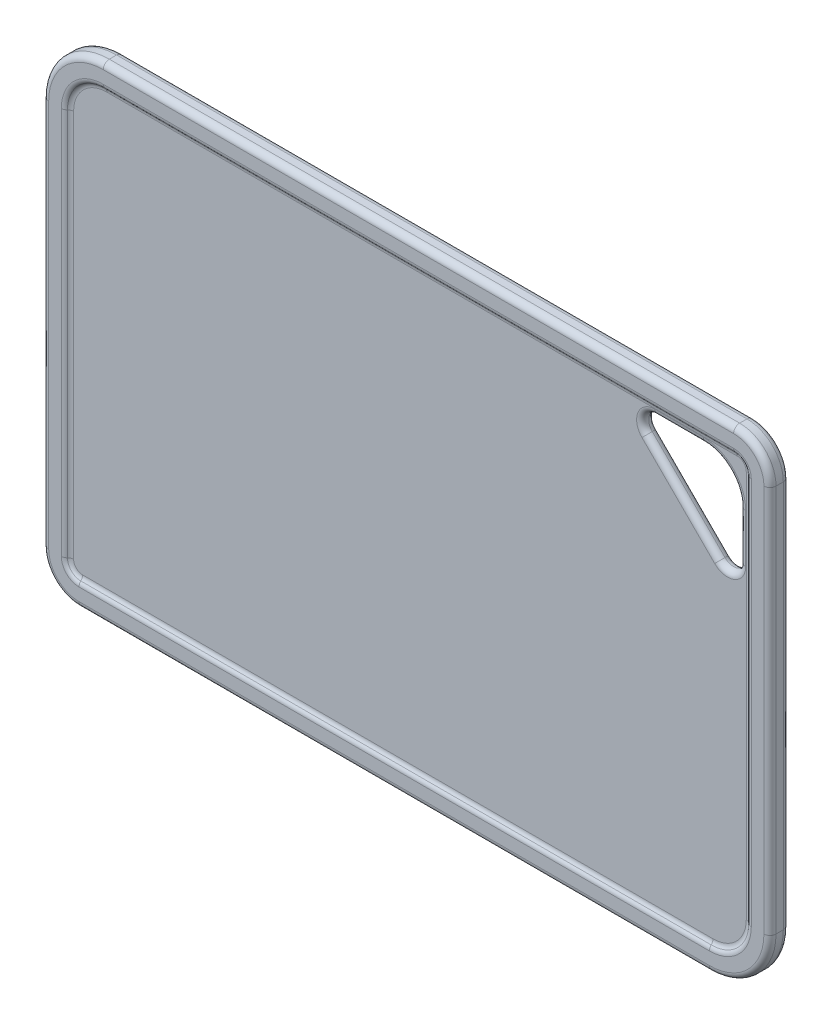
SolidWorks part; units mm, degrees
ref_plane "Front Plane" through (0, 0, 0) normal (0, 0, 1) x (1, 0, 0)
ref_plane "Top Plane" through (0, 0, 0) normal (0, 1, 0) x (1, 0, 0)
ref_plane "Right Plane" through (0, 0, 0) normal (1, 0, 0) x (0, 0, -1)
sketch "Sketch1" plane through (0, 0, 0) normal (0, 0, 1) x (1, 0, 0)
  line L1 (-190.5, -127) -> (190.5, -127)
  line L2 (-190.5, -127) -> (-190.5, 127)
  line L3 (-190.5, 127) -> (190.5, 127)
  line L4 (190.5, -127) -> (190.5, 127)
  line L5 (-190.5, -127) -> (190.5, 127) construction
  line L6 (-190.5, 127) -> (190.5, -127) construction
  point P0 (0, 0)
  dimension "D1" = 381
  dimension "D2" = 254
extrude "Boss-Extrude1" add sketch "Sketch1" along normal mid plane 6.35
fillet "Fillet5" radius 19.05 2 edges at (-190.5, -127, 0) (190.5, 127, 0)
fillet "Fillet4" radius 31.75 2 edges at (190.5, -127, 0) (-190.5, 127, 0)
sketch "Sketch2" plane through (0, 0, 3.175) normal (0, 0, 1) x (1, 0, 0)
  line L4 (-171.45, -127) -> (158.75, -127)
  line L5 (190.5, -95.25) -> (190.5, 107.95)
  line L6 (171.45, 127) -> (-158.75, 127)
  line L7 (-190.5, 95.25) -> (-190.5, -107.95)
  line L8 (-171.45, -127) -> (158.75, -127)
  line L9 (190.5, -95.25) -> (190.5, 107.95)
  line L10 (171.45, 127) -> (-158.75, 127)
  line L11 (-171.45, -114.3) -> (158.75, -114.3)
  line L12 (177.8, -95.25) -> (177.8, 107.95)
  line L13 (171.45, 114.3) -> (-158.75, 114.3)
  line L14 (-177.8, 95.25) -> (-177.8, -107.95)
  line L15 (-171.45, -114.3) -> (158.75, -114.3)
  line L16 (177.8, -95.25) -> (177.8, 107.95)
  line L17 (171.45, 114.3) -> (-158.75, 114.3)
  line L18 (-177.8, 95.25) -> (-177.8, -107.95)
  line L19 (-190.5, 95.25) -> (-190.5, -107.95)
  arc A4 (158.75, -114.3) -> (177.8, -95.25) centre (158.75, -95.25) ccw
  arc A5 (190.5, 107.95) -> (171.45, 127) centre (171.45, 107.95) ccw
  arc A6 (158.75, -114.3) -> (177.8, -95.25) centre (158.75, -95.25) ccw
  arc A7 (-158.75, 114.3) -> (-177.8, 95.25) centre (-158.75, 95.25) ccw
  arc A8 (-158.75, 114.3) -> (-177.8, 95.25) centre (-158.75, 95.25) ccw
  arc A9 (177.8, 107.95) -> (171.45, 114.3) centre (171.45, 107.95) ccw
  arc A10 (-177.8, -107.95) -> (-171.45, -114.3) centre (-171.45, -107.95) ccw
  arc A13 (177.8, 107.95) -> (171.45, 114.3) centre (171.45, 107.95) ccw
  arc A17 (190.5, 107.95) -> (171.45, 127) centre (171.45, 107.95) ccw
  arc A20 (158.75, -127) -> (190.5, -95.25) centre (158.75, -95.25) ccw
  arc A21 (158.75, -127) -> (190.5, -95.25) centre (158.75, -95.25) ccw
  arc A22 (-158.75, 127) -> (-190.5, 95.25) centre (-158.75, 95.25) ccw
  arc A23 (-158.75, 127) -> (-190.5, 95.25) centre (-158.75, 95.25) ccw
  arc A24 (-177.8, -107.95) -> (-171.45, -114.3) centre (-171.45, -107.95) ccw
  arc A26 (-190.5, -107.95) -> (-171.45, -127) centre (-171.45, -107.95) ccw
  arc A27 (-190.5, -107.95) -> (-171.45, -127) centre (-171.45, -107.95) ccw
  dimension "D1" = 12.7
  dimension "D2" = 0
extrude "Boss-Extrude2" add sketch "Sketch2" along normal blind 1.905
mirror "Mirror1" about plane through (0, 0, 0) normal (0, 0, 1) of "Boss-Extrude2"
sketch "Sketch3" plane through (0, 0, 3.175) normal (0, 0, 1) x (1, 0, 0)
  line L0 (153.67, 109.22) -> (128.27, 109.22)
  line L1 (172.72, 90.17) -> (172.72, 64.77)
  line L2 (171.45, 114.3) -> (-158.75, 114.3) construction
  line L3 (177.8, -95.25) -> (177.8, 107.95) construction
  line L4 (123.7799, 98.3799) -> (161.8799, 60.2799)
  arc A0 (153.67, 109.22) -> (172.72, 90.17) centre (153.67, 90.17) cw
  arc A1 (190.5, 107.95) -> (171.45, 127) centre (171.45, 107.95) ccw construction
  arc A2 (128.27, 109.22) -> (123.7799, 98.3799) centre (128.27, 102.87) ccw
  arc A3 (161.8799, 60.2799) -> (172.72, 64.77) centre (166.37, 64.77) ccw
  point P16 (151.0397, 39.2065)
  dimension "D4" = 6.35
  dimension "D1" = 5.08
  dimension "D2" = 5.08
  dimension "D3" = 45
  dimension "D5" = 25.4
extrude "Cut-Extrude1" cut sketch "Sketch3" against normal through all
fillet "Fillet9" radius 3.175 41 edges at (175.9401, 112.4401, -5.08) (177.8, 6.35, -5.08) (172.2204, -108.7204, -5.08) (-6.35, -114.3, -5.08) (-175.9401, -112.4401, -5.08) (-177.8, -6.35, -5.08) (-172.2204, 108.7204, -5.08) (175.9401, 112.4401, 5.08) (177.8, 6.35, 5.08) (172.2204, -108.7204, 5.08) (-6.35, -114.3, 5.08) (-175.9401, -112.4401, 5.08) (-177.8, -6.35, 5.08) (-172.2204, 108.7204, 5.08) (6.35, 114.3, -5.08) (6.35, 114.3, 5.08) (184.9204, 121.4204, 5.08) (190.5, 6.35, 5.08) (181.2006, -117.7006, 5.08) (-6.35, -127, 5.08) (-184.9204, -121.4204, 5.08) (-190.5, -6.35, 5.08) (-181.2006, 117.7006, 5.08) (184.9204, 121.4204, -5.08) (190.5, 6.35, -5.08) (181.2006, -117.7006, -5.08) (-181.2006, 117.7006, -5.08) (6.35, 127, 5.08) (6.35, 127, -5.08) (122.4034, 105.3, -3.175) (142.8299, 79.3299, -3.175) (168.8, 58.9034, -3.175) (172.72, 77.47, -3.175) (167.1404, 103.6404, -3.175) (172.72, 77.47, 3.175) (168.8, 58.9034, 3.175) (142.8299, 79.3299, 3.175) (122.4034, 105.3, 3.175) (140.97, 109.22, 3.175) (140.97, 109.22, -3.175) (167.1404, 103.6404, 3.175)
fillet "Fillet8" radius 3.175 16 edges at (177.8, 6.35, 3.175) (172.2204, -108.7204, 3.175) (-6.35, -114.3, 3.175) (-175.9401, -112.4401, 3.175) (-177.8, -6.35, 3.175) (-172.2204, 108.7204, 3.175) (6.35, 114.3, 3.175) (175.9401, 112.4401, -3.175) (177.8, 6.35, -3.175) (172.2204, -108.7204, -3.175) (-6.35, -114.3, -3.175) (-175.9401, -112.4401, -3.175) (-177.8, -6.35, -3.175) (-172.2204, 108.7204, -3.175) (175.9401, 112.4401, 3.175) (6.35, 114.3, -3.175)
